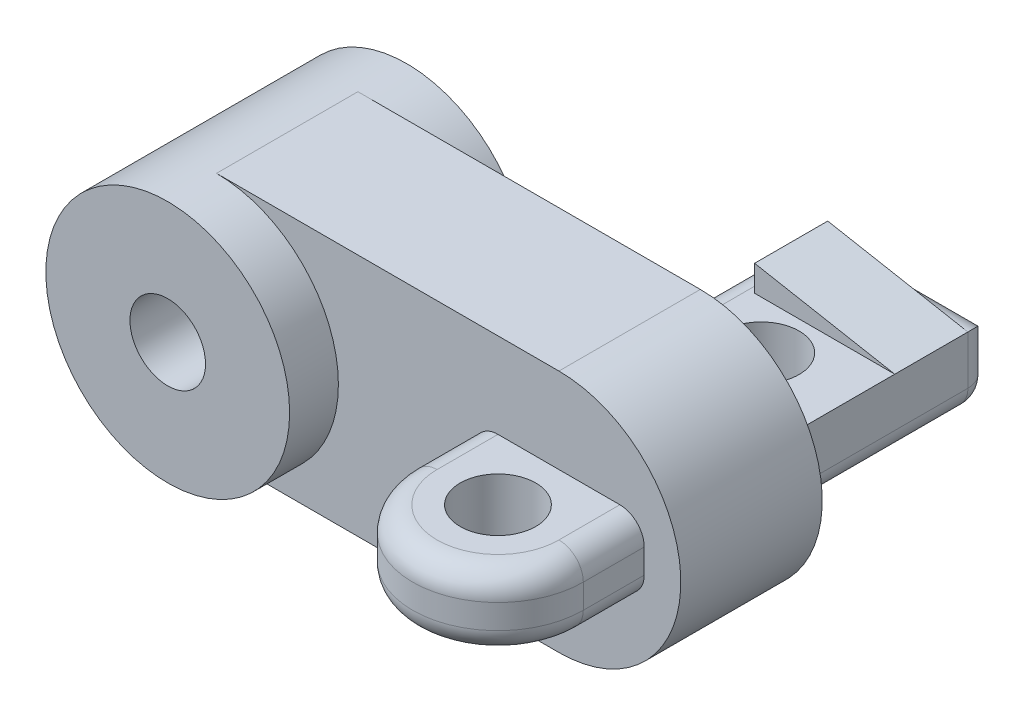
SolidWorks part; units mm, degrees
ref_plane "Plan de face" through (0, 0, 0) normal (0, 0, 1) x (1, 0, 0)
ref_plane "Plan de dessus" through (0, 0, 0) normal (0, 1, 0) x (1, 0, 0)
ref_plane "Plan de droite" through (0, 0, 0) normal (1, 0, 0) x (0, 0, -1)
sketch "Esquisse1" plane through (0, 0, 0) normal (0, 0, 1) x (1, 0, 0)
  circle A0 centre (0, 0) radius 5
  circle A1 centre (0, 0) radius 1.55
  dimension "D1" = 3.1
  dimension "D2" = 10
extrude "Boss.-Extru.1" add sketch "Esquisse1" along normal blind 9.8
sketch "Sketch8" plane through (0, 0, 0) normal (0, 0, -1) x (-1, 0, 0)
  line L0 (0, 5) -> (-14.0462, 5)
  line L1 (0, -5) -> (-14.0462, -5)
  circle A0 centre (0, 0) radius 5 construction
  arc A1 (0, 5) -> (0, -5) centre (0, 0) ccw
  arc A2 (-14.0462, 5) -> (-14.0462, -5) centre (-14.0462, 0) ccw
extrude "Boss-Extrude7" add sketch "Sketch8" against normal up to surface (9.8 mm away) up to face at (5, 0, 9.8)
ref_plane "Plane1" through (0, 0, 4.9) normal (0, 0, 1) x (1, 0, 0)
sketch "Sketch12" plane through (0, 0, 0) normal (0, 0, -1) x (-1, 0, 0)
  line L0 (-14.0462, 5) -> (-7.0231, 5)
  line L1 (0, 5) -> (-14.0462, 5) construction
  line L3 (-14.0462, -5) -> (0, -5) construction
  line L4 (-7.0231, -5) -> (-14.0462, -5)
  line L5 (-7.0231, 5) -> (0, 5)
  line L6 (-7.0231, -5) -> (0, -5)
  arc A0 (-14.0462, 5) -> (-14.0462, -5) centre (-14.0462, 0) ccw
  arc A1 (0, 5) -> (0, -5) centre (0, 0) ccw
extrude "Cut-Extrude3" cut sketch "Sketch12" against normal blind 2
mirror "Mirror3" about plane through (0, 0, 4.9) normal (0, 0, 1) of "Cut-Extrude3"
ref_plane "Plane3" through (0, 0, 0) normal (0, 1, 0) x (1, 0, 0)
sketch "Sketch14" plane through (0, 0, 0) normal (0, 1, 0) x (1, 0, 0)
  line L0 (14.0462, -4.9) -> (14.0462, 49995.1) construction
  line L1 (14.0462, -7.8) -> (14.0462, -2) construction
  line L2 (10.5462, -2) -> (17.5462, -2)
  line L3 (0, -2) -> (14.0462, -2) construction
  line L4 (19.0462, -2) -> (14.0462, -2) construction
  line L5 (17.5462, -2) -> (17.5462, 0.5)
  line L6 (10.5462, -2) -> (10.5462, 0.5)
  arc A0 (10.5462, 0.5) -> (17.5462, 0.5) centre (14.0462, 0.5) cw
  circle A1 centre (14.0462, 0.5) radius 1.55
  point P4 (14.0462, -4.9)
  dimension "D3" = 3.1
  dimension "D1" = 3.5
  dimension "D2" = 2.5
extrude "Boss-Extrude11" add sketch "Sketch14" along normal blind 1.5 and the other way blind 1.5
mirror "Mirror4" about plane through (0, 0, 4.9) normal (0, 0, 1) of "Boss-Extrude11"
sketch "Sketch15" plane through (0, 1.5, 0) normal (0, 1, 0) x (1, 0, 0)
  line L2 (10.5462, 0.5) -> (10.5462, 6.4761)
  line L3 (17.5462, 0.5) -> (17.5462, 6.4761)
  line L4 (10.5462, 6.4761) -> (17.5462, 6.4761)
  arc A3 (10.5462, 0.5) -> (17.5462, 0.5) centre (14.0462, 0.5) cw
  arc A4 (17.5462, 0.5) -> (10.5462, 0.5) centre (14.0462, 0.5) ccw construction
extrude "Boss-Extrude12" add sketch "Sketch15" against normal up to surface (3 mm away) up to face at (14.0462, -1.5, 9.925)
sketch "Sketch23" plane through (0, 0, -6.4761) normal (0, 0, -1) x (-1, 0, 0)
  line L0 (-17.5462, 1.5) -> (-11.7962, 2.5657)
  line L2 (-11.7962, 1.5) -> (-17.5462, 1.5)
  line L3 (-17.5462, 1.5) -> (-10.5462, 1.5) construction
  line L4 (-11.7962, 2.5657) -> (-11.7962, 1.5)
  line L5 (-10.5462, -1.5) -> (-10.5462, 1.5) construction
  point P3 (-11.6045, 3.0921)
  point P6 (-11.8864, 2.703)
  dimension "D1" = 10.5
  dimension "D2" = 1.25
extrude "Boss-Extrude17" add sketch "Sketch23" against normal blind 3 from offset 1 offset against normal yes
fillet "Fillet3" radius 1 6 edges at (17.5462, 1.5, 9.05) (10.5462, 1.5, 9.05) (10.5462, -1.5, 9.05) (14.0462, -1.5, 13.8) (14.0462, 1.5, 13.8) (17.5462, -1.5, 9.05)
fillet "Fillet5" radius 1 7 edges at (14.0462, 1.5, -6.4761) (17.5462, 0, -6.4761) (10.5462, 0, -6.4761) (10.5462, 1.5, -2.238) (10.5462, -1.5, -2.238) (17.5462, -1.5, -2.238) (14.0462, -1.5, -6.4761)
